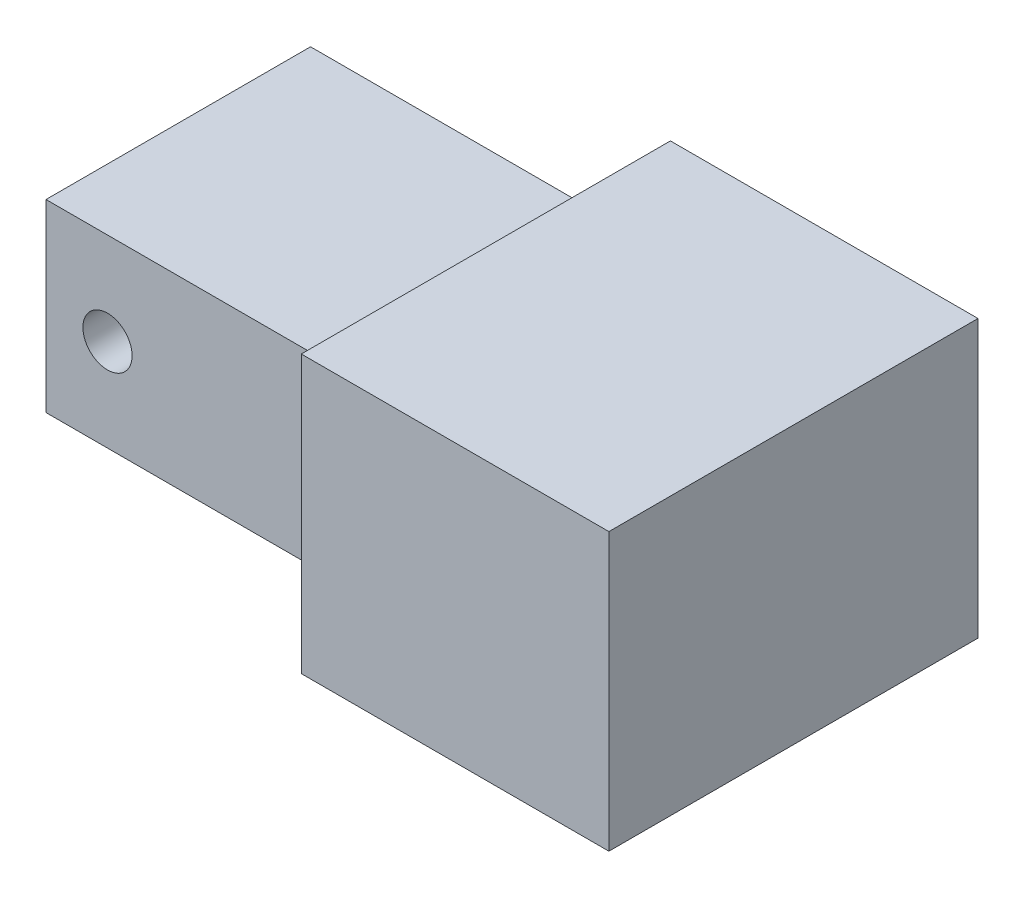
SolidWorks part; units mm, degrees
ref_plane "Front Plane" through (0, 0, 0) normal (0, 0, 1) x (1, 0, 0)
ref_plane "Top Plane" through (0, 0, 0) normal (0, 1, 0) x (1, 0, 0)
ref_plane "Right Plane" through (0, 0, 0) normal (1, 0, 0) x (0, 0, -1)
sketch "Sketch1" plane through (0, 0, 0) normal (0, 0, 1) x (1, 0, 0)
  line L0 (-50, -15) -> (-50, 15)
  line L1 (-50, 15) -> (50, 15)
  line L3 (-50, -15) -> (50, -15)
  line L4 (50, 15) -> (50, -15)
  line L5 (-50, 15) -> (50, -15) construction
  line L6 (-50, -15) -> (50, 15) construction
  circle A0 centre (-40, 0) radius 4
  point P0 (0, 0)
  dimension "D3" = 8
  dimension "D2" = 100
  dimension "D4" = 40
  dimension "D6" = 30
extrude "Boss-Extrude1" add sketch "Sketch1" along normal mid plane 43
sketch "Sketch2" plane through (0, 0, 0) normal (0, 1, 0) x (1, 0, 0)
  line L0 (50, -21.5) -> (50, 21.5) construction
  line L1 (0, 30) -> (50, 30)
  line L2 (0, 30) -> (0, -30)
  line L3 (0, -30) -> (50, -30)
  line L4 (50, 30) -> (50, -30)
  line L5 (0, 30) -> (50, -30) construction
  line L6 (0, -30) -> (50, 30) construction
  point P0 (25, 0)
  point P7 (0, 0)
  dimension "D1" = 50
  dimension "D2" = 60
extrude "Boss-Extrude2" add sketch "Sketch2" along normal mid plane 45
